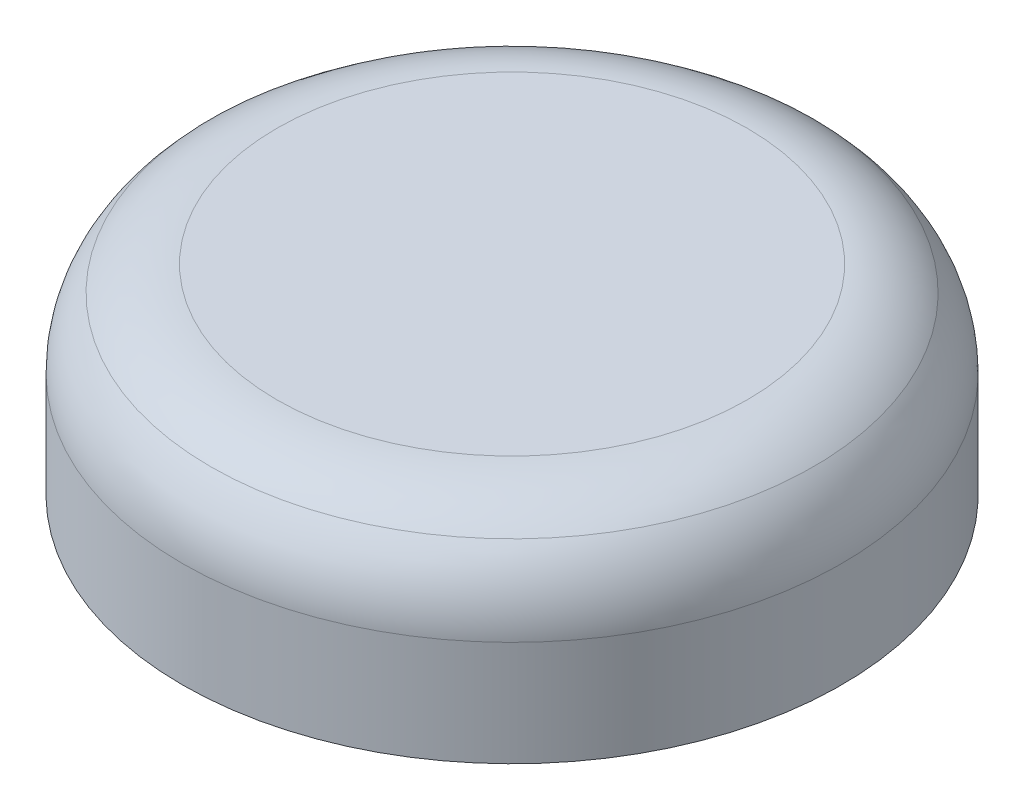
SolidWorks part; units mm, degrees
ref_plane "Front Plane" through (0, 0, 0) normal (0, 0, 1) x (1, 0, 0)
ref_plane "Top Plane" through (0, 0, 0) normal (0, 1, 0) x (1, 0, 0)
ref_plane "Right Plane" through (0, 0, 0) normal (1, 0, 0) x (0, 0, -1)
sketch "Sketch1" plane through (0, 0, 0) normal (0, 1, 0) x (1, 0, 0)
  circle A0 centre (0, 0) radius 30
  circle A1 centre (0, 0) radius 33
  dimension "D1" = 60
  dimension "D2" = 66
extrude "Boss-Extrude2" add sketch "Sketch1" along normal blind 15 contours A1 A0
sketch "Sketch3" plane through (0, 0, 0) normal (0, 0, 1) x (1, 0, 0)
  line L0 (0, 20) -> (-23.5509, 20)
  line L1 (-30.1653, 17.5) -> (-33, 15)
  line L2 (0, 15) -> (0, 20) construction
  line L3 (33, 15) -> (-33, 15) construction
  line L4 (-30, 15) -> (-28.7924, 15.8088)
  line L5 (-23.2278, 17.5) -> (0, 17.5)
  line L6 (0, 20) -> (0, 17.5)
  line L7 (-33, 15) -> (-30, 15)
  arc A0 (-30.1653, 17.5) -> (-23.5509, 20) centre (-23.5509, 10) cw
  arc A1 (-28.7924, 15.8088) -> (-23.2278, 17.5) centre (-23.2278, 7.5) cw
  dimension "D1" = 10
  dimension "D4" = 10
  dimension "D2" = 5
  dimension "D3" = 2.5
  dimension "D5" = 0.8088
revolve "Revolve1" add sketch "Sketch3" angle 360 about L2
sketch "Sketch4" plane through (0, 0, 0) normal (0, -1, 0) x (1, 0, 0)
  circle A0 centre (0, 0) radius 25.5
  circle A1 centre (0, 0) radius 22.55
  dimension "D1" = 51
  dimension "D2" = 45.1
extrude "Boss-Extrude3" add sketch "Sketch4" against normal up to surface (17.2384 mm away) up to face at (0, 17.5, -23.2278)
fillet "Fillet1" radius 10 1 edges at (0, 15, 33)
